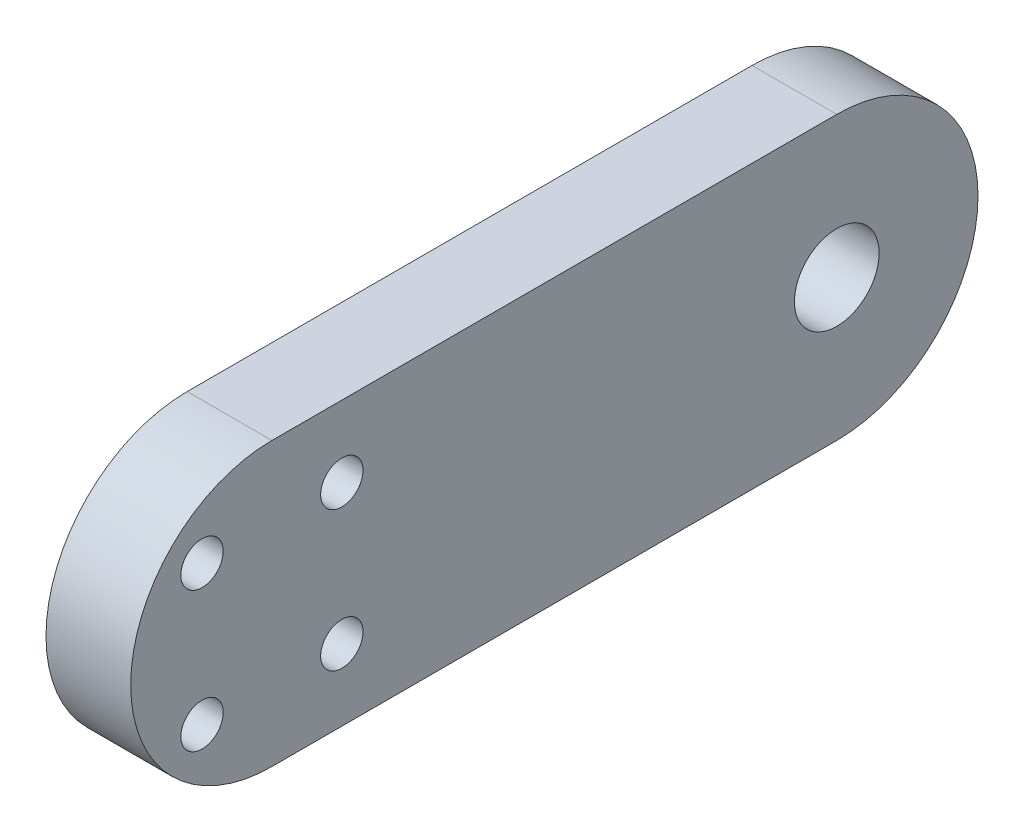
SolidWorks part; units mm, degrees
ref_plane "Front Plane" through (0, 0, 0) normal (0, 0, 1) x (1, 0, 0)
ref_plane "Top Plane" through (0, 0, 0) normal (0, 1, 0) x (1, 0, 0)
ref_plane "Right Plane" through (0, 0, 0) normal (1, 0, 0) x (0, 0, -1)
sketch "length (ref to equation file)" plane through (0, 0, 0) normal (1, 0, 0) x (0, 0, -1)
  line L0 (0, 0) -> (40, 0)
  dimension "D1" = 40
ref_axis "motor pivot" through (0, 0, 0) along (1, 0, 0)
ref_axis "pivot w/ link 2" through (0, 0, -40) along (1, 0, 0)
sketch "Sketch1" plane through (0, 0, 0) normal (1, 0, 0) x (0, 0, -1)
  line L0 (40, 0) -> (0, 0) construction
  line L1 (40, -10) -> (0, -10)
  line L2 (40, 10) -> (0, 10)
  arc A0 (40, -10) -> (40, 10) centre (40, 0) ccw
  arc A1 (0, 10) -> (0, -10) centre (0, 0) ccw
  point P4 (20, 0)
  dimension "D1" = 20
extrude "Boss-Extrude1" add sketch "Sketch1" along normal mid plane 6 contours L2 A1 L1 A0
sketch "Sketch2" plane through (0, 0, 0) normal (1, 0, 0) x (0, 0, -1)
  arc A0 (-3.8891, -3.8891) -> (-6.0104, -6.0104) centre (-4.9497, -4.9497) ccw construction
  arc A1 (-6.0104, -6.0104) -> (-3.8891, -3.8891) centre (-4.9497, -4.9497) ccw construction
  arc A2 (6.0104, -3.8891) -> (3.8891, -6.0104) centre (4.9497, -4.9497) ccw construction
  arc A3 (3.8891, -6.0104) -> (6.0104, -3.8891) centre (4.9497, -4.9497) ccw construction
  arc A4 (-6.0104, 3.8891) -> (-3.8891, 6.0104) centre (-4.9497, 4.9497) ccw construction
  arc A5 (-3.8891, 6.0104) -> (-6.0104, 3.8891) centre (-4.9497, 4.9497) ccw construction
  arc A6 (6.0104, 6.0104) -> (3.8891, 3.8891) centre (4.9497, 4.9497) ccw construction
  arc A7 (3.8891, 3.8891) -> (6.0104, 6.0104) centre (4.9497, 4.9497) ccw construction
  arc A8 (-3.8891, -3.8891) -> (-6.0104, -6.0104) centre (-4.9497, -4.9497) ccw construction
  arc A9 (-6.0104, -6.0104) -> (-3.8891, -3.8891) centre (-4.9497, -4.9497) ccw construction
  arc A10 (6.0104, -3.8891) -> (3.8891, -6.0104) centre (4.9497, -4.9497) ccw construction
  arc A11 (3.8891, -6.0104) -> (6.0104, -3.8891) centre (4.9497, -4.9497) ccw construction
  arc A12 (-6.0104, 3.8891) -> (-3.8891, 6.0104) centre (-4.9497, 4.9497) ccw construction
  arc A13 (-3.8891, 6.0104) -> (-6.0104, 3.8891) centre (-4.9497, 4.9497) ccw construction
  arc A14 (6.0104, 6.0104) -> (3.8891, 3.8891) centre (4.9497, 4.9497) ccw construction
  arc A15 (3.8891, 3.8891) -> (6.0104, 6.0104) centre (4.9497, 4.9497) ccw construction
  circle A16 centre (4.9497, 4.9497) radius 1.5
  circle A17 centre (4.9497, -4.9497) radius 1.5
  circle A18 centre (-4.9497, -4.9497) radius 1.5
  circle A19 centre (-4.9497, 4.9497) radius 1.5
extrude "Cut-Extrude1" cut sketch "Sketch2" against normal through all both and the other way through all
sketch "Sketch3" plane through (0, 0, 0) normal (1, 0, 0) x (0, 0, -1)
  circle A0 centre (40, 0) radius 3
  dimension "D1" = 6
extrude "Cut-Extrude2" cut sketch "Sketch3" against normal through all both and the other way through all
equation "\"link 1\" = 40mm"
equation "\"D1@length (ref to equation file)\" = \"link 1\""
equation "\"link 1 thickness\" = 6mm"
equation "\"D1@Boss-Extrude1\"=\"link 1 thickness\""
equation "\"motor center z\" = 60mm"
equation "\"motor center y\" = 20mm"
equation "\"link 2\"= 90mm"
equation "\"pivot height\"= 100mm"
equation "\"beam length\"= 400mm"
equation "\"camera height\"= 250mm"
equation "\"link height\" = 20mm"
equation "\"beam width\"= 28.5mm"
equation "\"beam side wall thickness\"= 3mm"
equation "\"D1@Sketch1\"=\"link height\""
